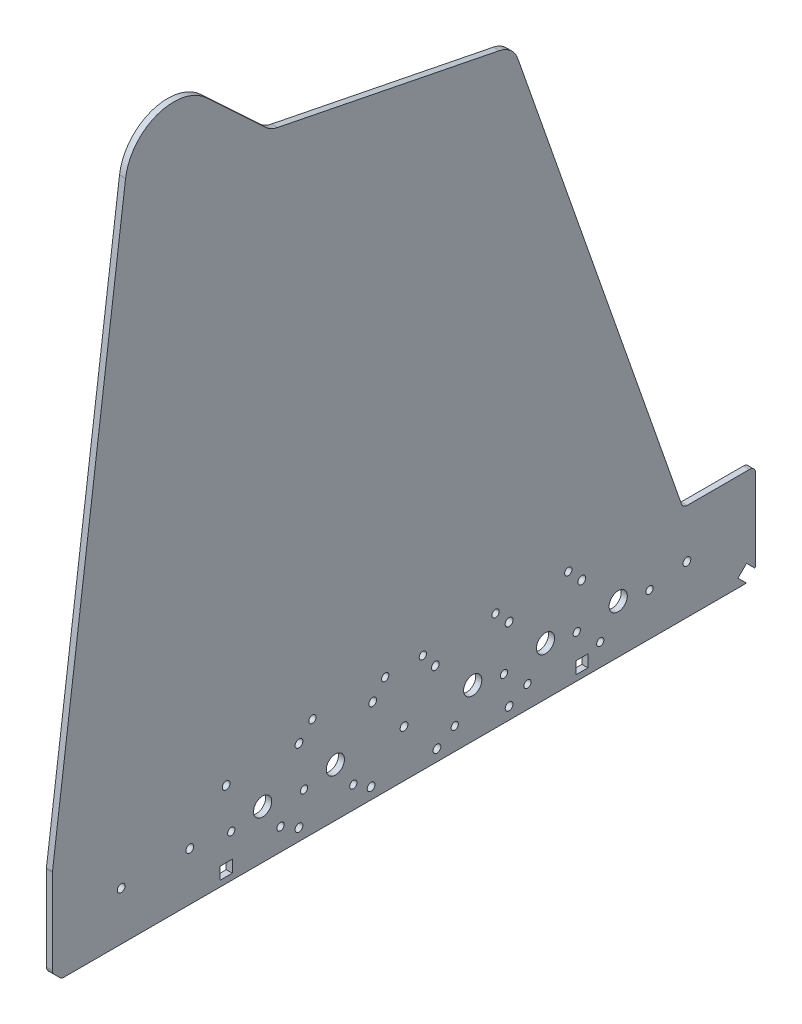
SolidWorks part; units mm, degrees
ref_plane "Front Plane" through (0, 0, 0) normal (0, 0, 1) x (1, 0, 0)
ref_plane "Top Plane" through (0, 0, 0) normal (0, 1, 0) x (1, 0, 0)
ref_plane "Right Plane" through (0, 0, 0) normal (1, 0, 0) x (0, 0, -1)
sketch "Sketch1" plane through (0, 0, 0) normal (1, 0, 0) x (0, 0, -1)
  line L0 (-184.15, -24.6062) -> (184.15, -24.6062)
  line L1 (184.15, -24.6062) -> (184.15, 26.1938)
  line L2 (184.15, 26.1938) -> (146.05, 26.1937)
  line L3 (146.05, 26.1937) -> (57.15, 280.1938)
  line L5 (-145.839, 321.5609) -> (-184.15, 26.1938)
  line L6 (-184.15, 26.1938) -> (-184.15, -24.6062)
  line L7 (-184.15, 350.0437) -> (184.15, 350.0437) construction
  line L8 (57.15, 280.1938) -> (-69.85, 305.5938)
  line L9 (-69.85, 305.5938) -> (-103.3099, 336.854)
  arc A0 (-103.3099, 336.854) -> (-145.839, 321.5609) centre (-120.65, 318.2937) ccw
  point P8 (0, -24.6062)
  dimension "D1" = 368.3
  dimension "D7" = 25.4
  dimension "D2" = 50.8
  dimension "D3" = 38.1
  dimension "D4" = 24.6062
  dimension "D5" = 374.65
  dimension "D6" = 304.8
  dimension "D8" = 342.9
  dimension "D9" = 127
  dimension "D10" = 304.8
  dimension "D11" = 25.4
  dimension "D12" = 127
extrude "Boss-Extrude1" add sketch "Sketch1" along normal blind 3.175
chamfer "Chamfer1" distance 4.7625 angle 45 2 edges at (1.5875, -24.6062, 184.15) (1.5875, -24.6062, -184.15)
fillet "Fillet1" radius 12.7 2 edges at (1.5875, 305.5938, 69.85) (1.5875, 280.1938, -57.15)
fillet "Fillet2" radius 3.175 3 edges at (1.5875, 26.1938, 184.15) (1.5875, 26.1938, -184.15) (1.5875, 26.1937, -146.05)
fillet "Fillet3" radius 3.175 4 edges at (1.5875, -19.8438, -184.15) (1.5875, -24.6062, -179.3875) (1.5875, -19.8437, 184.15) (1.5875, -24.6062, 179.3875)
sketch "Sketch16" plane through (3.175, 0, 0) normal (1, 0, 0) x (0, 0, -1)
  circle A0 centre (112.1746, 0.7937) radius 4.7625
  circle A1 centre (74.0746, 0.7937) radius 4.7625
  circle A2 centre (35.9746, 0.7937) radius 4.7625
  circle A3 centre (-35.9746, 0.7938) radius 4.7625
  circle A4 centre (-74.0746, 0.7938) radius 4.7625
  dimension "D1" = 9.525
extrude "Cut-Extrude1" cut sketch "Sketch16" against normal up to next
sketch "Sketch21" plane through (3.175, 0, 0) normal (1, 0, 0) x (0, 0, -1)
  circle A0 centre (-148.1579, 0.7937) radius 2.032
  circle A1 centre (-112.1746, 0.7937) radius 2.032
  circle A2 centre (0, 0) radius 2.032
  circle A3 centre (148.1579, 0.7938) radius 2.032
  dimension "D1" = 4.064
extrude "Cut-Extrude2" cut sketch "Sketch21" against normal up to next
sketch "Sketch22" plane through (3.175, 0, 0) normal (1, 0, 0) x (0, 0, -1)
  line L0 (-96.2996, -15.1473) -> (-89.9496, -15.1473) construction
  line L1 (-96.2996, -15.1473) -> (-89.9496, -15.1473)
  line L2 (-96.2996, -15.1473) -> (-96.2996, -21.4973)
  line L3 (-96.2996, -21.4973) -> (-89.9496, -21.4973)
  line L4 (-89.9496, -15.1473) -> (-89.9496, -21.4973)
  line L5 (-96.2996, -15.1473) -> (-89.9496, -21.4973) construction
  line L6 (-96.2996, -21.4973) -> (-89.9496, -15.1473) construction
  line L7 (-89.9496, -15.1473) -> (-89.9496, -19.8734) construction
  line L77 (179.3875, -24.6062) -> (183.8776, -20.1161)
  line L78 (179.3875, -24.6062) -> (174.8974, -20.1161)
  line L79 (183.8776, -20.1161) -> (179.3875, -15.626)
  line L80 (174.8974, -20.1161) -> (179.3875, -15.626)
  line L81 (180.3174, -23.6763) -> (183.2201, -20.7737) construction
  line L82 (-178.0724, -24.6062) -> (178.0724, -24.6062) construction
  line L84 (89.9496, -21.4973) -> (96.2996, -21.4973)
  line L85 (89.9496, -21.4973) -> (89.9496, -15.1473)
  line L86 (89.9496, -15.1473) -> (96.2996, -15.1473)
  line L87 (96.2996, -21.4973) -> (96.2996, -15.1473)
  line L88 (89.9496, -21.4973) -> (96.2996, -15.1473) construction
  line L89 (89.9496, -15.1473) -> (96.2996, -21.4973) construction
  point P0 (-93.1246, -18.3223)
  point P19 (93.1246, -18.3223)
  dimension "D1" = 6.35
  dimension "D2" = 6.35
extrude "Cut-Extrude3" cut sketch "Sketch22" against normal up to next
sketch "Sketch23" plane through (3.175, 0, 0) normal (1, 0, 0) x (0, 0, -1)
  point P0 (-55.0246, -18.3223)
  point P3 (-55.0246, 19.9098)
  point P6 (-93.1246, 19.9098)
  point P9 (-17.2515, -18.6426)
  point P12 (-16.4124, 19.3854)
  point P15 (16.4124, 19.3854)
  point P18 (17.2515, -18.6426)
  point P21 (55.0246, -18.3223)
  point P27 (93.1246, 19.9098)
  point P30 (55.0246, 19.9098)
  point P41 (0, 0)
  point P42 (0, 0)
  point P43 (0, 0)
hole_wizard "#8 (0.16) Diameter Hole1" positions "Sketch23" profile "Sketch24" hole size "#8" standard "ANSI Inch" end condition up to next
sketch "Sketch24" plane through (3.175, -18.3223, 55.0246) normal (0, 1, 0) x (0, 0, -1)
  line L0 (0, 0) -> (0, 3.175)
  line L1 (0, 3.175) -> (2.032, 3.175)
  line L2 (2.032, 3.175) -> (2.032, 0)
  line L5 (2.032, 0) -> (0, 0)
  line L11 (0, -6.35) -> (0, 107.95) construction
  dimension "Thru Hole Dia." = 4.064
  dimension "Thru Hole Depth" = 3.175
sketch "Sketch25" plane through (3.175, 0, 0) normal (1, 0, 0) x (0, 0, -1)
  circle A0 centre (102.7672, -13.0003) radius 1.905 construction
  circle A1 centre (86.0486, 27.3622) radius 1.905 construction
  circle A2 centre (128.5804, -2.3081) radius 1.905 construction
  circle A3 centre (102.7672, -13.0003) radius 1.905
  circle A4 centre (86.0486, 27.3622) radius 1.905
  circle A5 centre (128.5804, -2.3081) radius 1.905
  circle A6 centre (64.6672, -13.0003) radius 1.905 construction
  circle A8 centre (-9.8486, 27.3622) radius 1.905 construction
  circle A10 centre (-47.9486, 27.3622) radius 1.905 construction
  circle A11 centre (-90.4804, -2.3081) radius 1.905 construction
  circle A12 centre (-64.6672, -13.0003) radius 1.905 construction
  circle A14 centre (-52.3804, -2.3081) radius 1.905 construction
  circle A15 centre (-26.5672, -13.0003) radius 1.905 construction
  circle A16 centre (9.8486, 27.3622) radius 1.905 construction
  circle A17 centre (26.5672, -13.0003) radius 1.905 construction
  circle A18 centre (47.9486, 27.3622) radius 1.905 construction
  circle A19 centre (52.3804, -2.3081) radius 1.905 construction
  circle A20 centre (90.4804, -2.3081) radius 1.905 construction
  circle A21 centre (-9.8486, 27.3622) radius 1.905
  circle A23 centre (-47.9486, 27.3622) radius 1.905
  circle A24 centre (-90.4804, -2.3081) radius 1.905
  circle A25 centre (-64.6672, -13.0003) radius 1.905
  circle A27 centre (-52.3804, -2.3081) radius 1.905
  circle A28 centre (-26.5672, -13.0003) radius 1.905
  circle A29 centre (9.8486, 27.3622) radius 1.905
  circle A30 centre (26.5672, -13.0003) radius 1.905
  circle A31 centre (47.9486, 27.3622) radius 1.905
  circle A32 centre (64.6672, -13.0003) radius 1.905
  circle A33 centre (52.3804, -2.3081) radius 1.905
  circle A34 centre (90.4804, -2.3081) radius 1.905
extrude "Cut-Extrude4" cut sketch "Sketch25" against normal up to next
